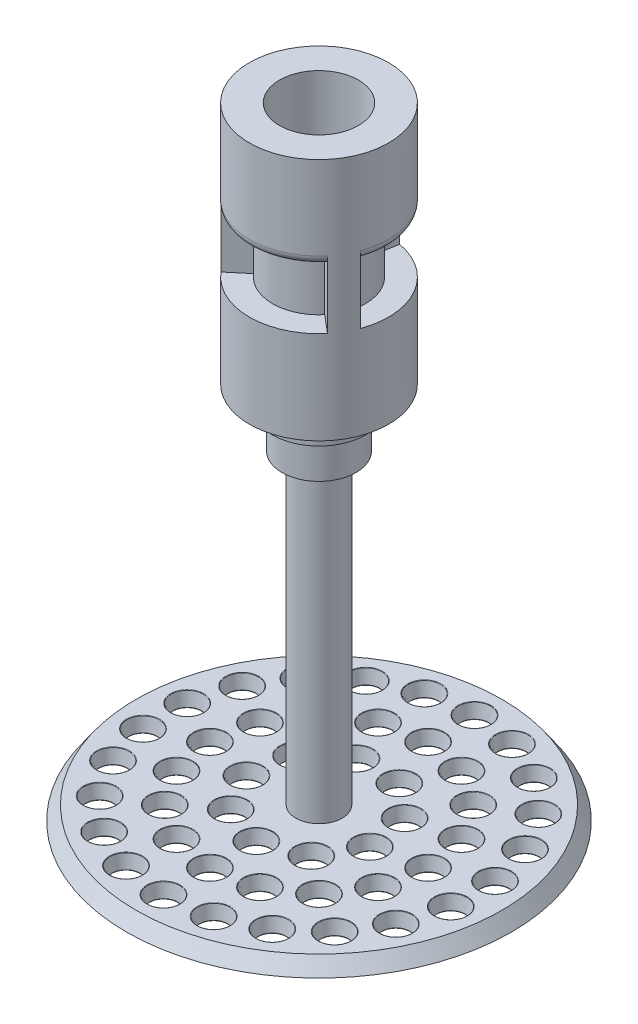
SolidWorks part; units mm, degrees
material "Nylon 101"
ref_plane "Alzado" through (0, 0, 0) normal (0, 0, 1) x (1, 0, 0)
ref_plane "Planta" through (0, 0, 0) normal (0, 1, 0) x (1, 0, 0)
ref_plane "Vista lateral" through (0, 0, 0) normal (1, 0, 0) x (0, 0, -1)
sketch "Croquis1" plane through (0, 0, 0) normal (0, 1, 0) x (1, 0, 0)
  circle A0 centre (0, 0) radius 41.5
  dimension "D1" = 83
extrude "Saliente-Extruir1" add sketch "Croquis1" along normal blind 3 draft 35
sketch "Croquis2" plane through (0, 3, 0) normal (0, 1, 0) x (1, 0, 0)
  circle A0 centre (0, 0) radius 5
  dimension "D1" = 10
extrude "Saliente-Extruir2" add sketch "Croquis2" along normal blind 66
sketch "Croquis3" plane through (0, 3, 0) normal (0, 1, 0) x (1, 0, 0)
  circle A0 centre (0, -13.5) radius 3.5
  circle A1 centre (-8.6776, -10.3416) radius 3.5
  circle A2 centre (-13.2949, -2.3443) radius 3.5
  circle A3 centre (-11.6913, 6.75) radius 3.5
  circle A4 centre (-4.6173, 12.6859) radius 3.5
  circle A5 centre (4.6173, 12.6859) radius 3.5
  circle A6 centre (11.6913, 6.75) radius 3.5
  circle A7 centre (13.2949, -2.3443) radius 3.5
  circle A8 centre (8.6776, -10.3416) radius 3.5
  circle A9 centre (0, -23.5) radius 3.5
  circle A10 centre (-8.9931, -21.7112) radius 3.5
  circle A11 centre (-16.617, -16.617) radius 3.5
  circle A12 centre (-21.7112, -8.9931) radius 3.5
  circle A13 centre (-23.5, 0) radius 3.5
  circle A14 centre (-21.7112, 8.9931) radius 3.5
  circle A15 centre (-16.617, 16.617) radius 3.5
  circle A16 centre (-8.9931, 21.7112) radius 3.5
  circle A17 centre (0, 23.5) radius 3.5
  circle A18 centre (8.9931, 21.7112) radius 3.5
  circle A19 centre (16.617, 16.617) radius 3.5
  circle A20 centre (21.7112, 8.9931) radius 3.5
  circle A21 centre (23.5, 0) radius 3.5
  circle A22 centre (21.7112, -8.9931) radius 3.5
  circle A23 centre (16.617, -16.617) radius 3.5
  circle A24 centre (8.9931, -21.7112) radius 3.5
  circle A25 centre (0, -33.5) radius 3.5
  circle A26 centre (-9.438, -32.143) radius 3.5
  circle A27 centre (-18.1115, -28.182) radius 3.5
  circle A28 centre (-25.3176, -21.9378) radius 3.5
  circle A29 centre (-30.4727, -13.9164) radius 3.5
  circle A30 centre (-33.159, -4.7675) radius 3.5
  circle A31 centre (-33.159, 4.7675) radius 3.5
  circle A32 centre (-30.4727, 13.9164) radius 3.5
  circle A33 centre (-25.3176, 21.9378) radius 3.5
  circle A34 centre (-18.1115, 28.182) radius 3.5
  circle A35 centre (-9.438, 32.143) radius 3.5
  circle A36 centre (0, 33.5) radius 3.5
  circle A37 centre (9.438, 32.143) radius 3.5
  circle A38 centre (18.1115, 28.182) radius 3.5
  circle A39 centre (25.3176, 21.9378) radius 3.5
  circle A40 centre (30.4727, 13.9164) radius 3.5
  circle A41 centre (33.159, 4.7675) radius 3.5
  circle A42 centre (33.159, -4.7675) radius 3.5
  circle A43 centre (30.4727, -13.9164) radius 3.5
  circle A44 centre (25.3176, -21.9378) radius 3.5
  circle A45 centre (18.1115, -28.182) radius 3.5
  circle A46 centre (9.438, -32.143) radius 3.5
  point P22 (0, 0)
  point P55 (0, 0)
  point P100 (0, 0)
  dimension "D1" = 7
  dimension "D4" = 7
  dimension "D7" = 7
  dimension "D2" = 13.5
  dimension "D5" = 10
  dimension "D8" = 10
  dimension "D3" = 9
  dimension "D6" = 16
  dimension "D9" = 22
extrude "Cortar-Extruir1" cut sketch "Croquis3" against normal through all draft 10
sketch "Croquis4" plane through (0, 69, 0) normal (0, 1, 0) x (1, 0, 0)
  circle A0 centre (0, 0) radius 8
  dimension "D1" = 16
extrude "Saliente-Extruir3" add sketch "Croquis4" along normal blind 8
sketch "Croquis5" plane through (0, 77, 0) normal (0, 1, 0) x (1, 0, 0)
  circle A0 centre (0, 0) radius 10
  dimension "D1" = 20
extrude "Saliente-Extruir4" add sketch "Croquis5" along normal blind 2.5
sketch "Croquis6" plane through (0, 79.5, 0) normal (0, 1, 0) x (1, 0, 0)
  circle A0 centre (0, 0) radius 8.5
  dimension "D1" = 17
extrude "Saliente-Extruir5" add sketch "Croquis6" along normal blind 2
sketch "Croquis7" plane through (0, 81.5, 0) normal (0, 1, 0) x (1, 0, 0)
  circle A0 centre (0, 0) radius 10
extrude "Saliente-Extruir6" add sketch "Croquis7" along normal blind 2.5
fillet "Redondeo3" radius 0.1 94 edges at (0, 3, 17) (0, 0, 16.471) (0, 3, 27) (0, 0, 26.471) (-8.6776, 3, 13.8416) (-8.6776, 0, 13.3126) (-13.2949, 3, 5.8443) (-13.2949, 0, 5.3153) (-11.6913, 3, -3.25) (-11.6913, 0, -3.779) (-4.6173, 3, -9.1859) (-4.6173, 0, -9.7148) (4.6173, 3, -9.1859) (4.6173, 0, -9.7148) (11.6913, 3, -3.25) (11.6913, 0, -3.779) (13.2949, 3, 5.8443) (13.2949, 0, 5.3153) (8.6776, 3, 13.8416) (8.6776, 0, 13.3126) (0, 3, 37) (0, 0, 36.471) (-8.9931, 3, 25.2112) (-8.9931, 0, 24.6822) (-16.617, 3, 20.117) (-16.617, 0, 19.588) (-21.7112, 3, 12.4931) (-21.7112, 0, 11.9641) (-23.5, 3, 3.5) (-23.5, 0, 2.971) (-21.7112, 3, -5.4931) (-21.7112, 0, -6.022) (-16.617, 3, -13.117) (-16.617, 0, -13.646) (-8.9931, 3, -18.2112) (-8.9931, 0, -18.7401) (0, 3, -20) (0, 0, -20.529) (8.9931, 3, -18.2112) (8.9931, 0, -18.7401) (16.617, 3, -13.117) (16.617, 0, -13.646) (21.7112, 3, -5.4931) (21.7112, 0, -6.022) (23.5, 3, 3.5) (23.5, 0, 2.971) (21.7112, 3, 12.4931) (21.7112, 0, 11.9641) (16.617, 3, 20.117) (16.617, 0, 19.588) (8.9931, 3, 25.2112) (8.9931, 0, 24.6822) (-9.438, 3, 35.643) (-9.438, 0, 35.114) (-18.1115, 3, 31.682) (-18.1115, 0, 31.153) (-25.3176, 3, 25.4378) (-25.3176, 0, 24.9089) (-30.4727, 3, 17.4164) (-30.4727, 0, 16.8874) (-33.159, 3, 8.2675) (-33.159, 0, 7.7386) (-33.159, 3, -1.2675) (-33.159, 0, -1.7965) (-30.4727, 3, -10.4164) (-30.4727, 0, -10.9454) (-25.3176, 3, -18.4378) (-25.3176, 0, -18.9668) (-18.1115, 3, -24.682) (-18.1115, 0, -25.211) (-9.438, 3, -28.643) (-9.438, 0, -29.172) (0, 3, -30) (0, 0, -30.529) (9.438, 3, -28.643) (9.438, 0, -29.172) (18.1115, 3, -24.682) (18.1115, 0, -25.211) (25.3176, 3, -18.4378) (25.3176, 0, -18.9668) (30.4727, 3, -10.4164) (30.4727, 0, -10.9454) (33.159, 3, -1.2675) (33.159, 0, -1.7965) (33.159, 3, 8.2675) (33.159, 0, 7.7386) (30.4727, 3, 17.4164) (30.4727, 0, 16.8874) (25.3176, 3, 25.4378) (25.3176, 0, 24.9089) (18.1115, 3, 31.682) (18.1115, 0, 31.153) (9.438, 3, 35.643) (9.438, 0, 35.114)
sketch "Sketch1" plane through (0, 0, 0) normal (1, 0, 0) x (0, 0, -1)
  line L0 (0, 84) -> (0, 138.0793) construction
  line L3 (-10, 84) -> (-10, 134)
  line L6 (-8.5, 84) -> (-8.5, 134)
  line L7 (10, 84) -> (-10, 84) construction
  line L8 (-8.5, 134) -> (-10, 134)
  line L9 (-8.5, 84) -> (-10, 84)
  dimension "D1" = 17
  dimension "D2" = 50
revolve "Revolve1" add sketch "Sketch1" angle 360 about L0
sketch "Sketch2" plane through (0, 134, 0) normal (0, 1, 0) x (1, 0, 0)
  line L0 (0, 0) -> (0, 22.8117) construction
  line L1 (-2.5, 9.6825) -> (-2.5, 12.1825)
  line L2 (-2.5, 12.1825) -> (2.5, 12.1825)
  line L3 (2.5, 12.1825) -> (2.5, 9.6825)
  circle A0 centre (0, 0) radius 10 construction
  arc A3 (2.5, 9.6825) -> (-2.5, 9.6825) centre (0, 0) ccw
  dimension "D1" = 5
  dimension "D2" = 2.5
extrude "Boss-Extrude1" [suppressed] add sketch "Sketch2" against normal blind 5
sketch "Sketch3" plane through (0, 0, 0) normal (0, 0, 1) x (1, 0, 0)
  line L6 (-10, 134) -> (-10, 114)
  line L12 (-10, 134) -> (-10, 81.5) construction
  line L13 (-10, 114) -> (-15, 114)
  line L14 (-15, 114) -> (-15, 134)
  line L15 (-15, 134) -> (-10, 134)
  line L16 (-10, 81.5) -> (-15, 81.5)
  line L17 (-15, 81.5) -> (-15, 101.5)
  line L18 (-15, 101.5) -> (-10, 101.5)
  line L19 (-10, 101.5) -> (-10, 81.5)
  line L20 (0, 0) -> (0, 51.2653) construction
  dimension "D1" = 20
  dimension "D2" = 5
  dimension "D3" = 20
revolve "Revolve2" add sketch "Sketch3" angle 360 about L20
sketch "Sketch4" plane through (0, 101.5, 0) normal (0, 1, 0) x (1, 0, 0)
  line L0 (-2.6047, 14.7721) -> (-1.7365, 9.8481)
  line L1 (0, 0) -> (0, 18.3358) construction
  line L2 (-2.6047, 14.7721) -> (0, 0) construction
  line L3 (2.6047, 14.7721) -> (1.7365, 9.8481)
  line L4 (14.0954, -5.1303) -> (9.3969, -3.4202)
  line L5 (11.4907, -9.6418) -> (7.6604, -6.4279)
  line L6 (-11.4907, -9.6418) -> (-7.6604, -6.4279)
  line L7 (-14.0954, -5.1303) -> (-9.3969, -3.4202)
  circle A0 centre (0, 0) radius 15 construction
  arc A1 (11.4907, -9.6418) -> (14.0954, -5.1303) centre (0, 0) ccw
  arc A2 (-14.0954, -5.1303) -> (-11.4907, -9.6418) centre (0, 0) ccw
  arc A5 (2.6047, 14.7721) -> (-2.6047, 14.7721) centre (0, 0) ccw
  circle A9 centre (0, 0) radius 10 construction
  arc A10 (-9.3969, -3.4202) -> (-7.6604, -6.4279) centre (0, 0) ccw
  arc A11 (1.7365, 9.8481) -> (-1.7365, 9.8481) centre (0, 0) ccw
  arc A12 (7.6604, -6.4279) -> (9.3969, -3.4202) centre (0, 0) ccw
  dimension "D1" = 20
  dimension "D2" = 3
extrude "Boss-Extrude2" add sketch "Sketch4" along direction (0, 1, 0) on the side of the normal up to next (12.5 mm away)
fillet "Fillet1" radius 2 3 edges at (-12.9904, 114, -7.5) (0, 114, 15) (12.9904, 114, -7.5)
